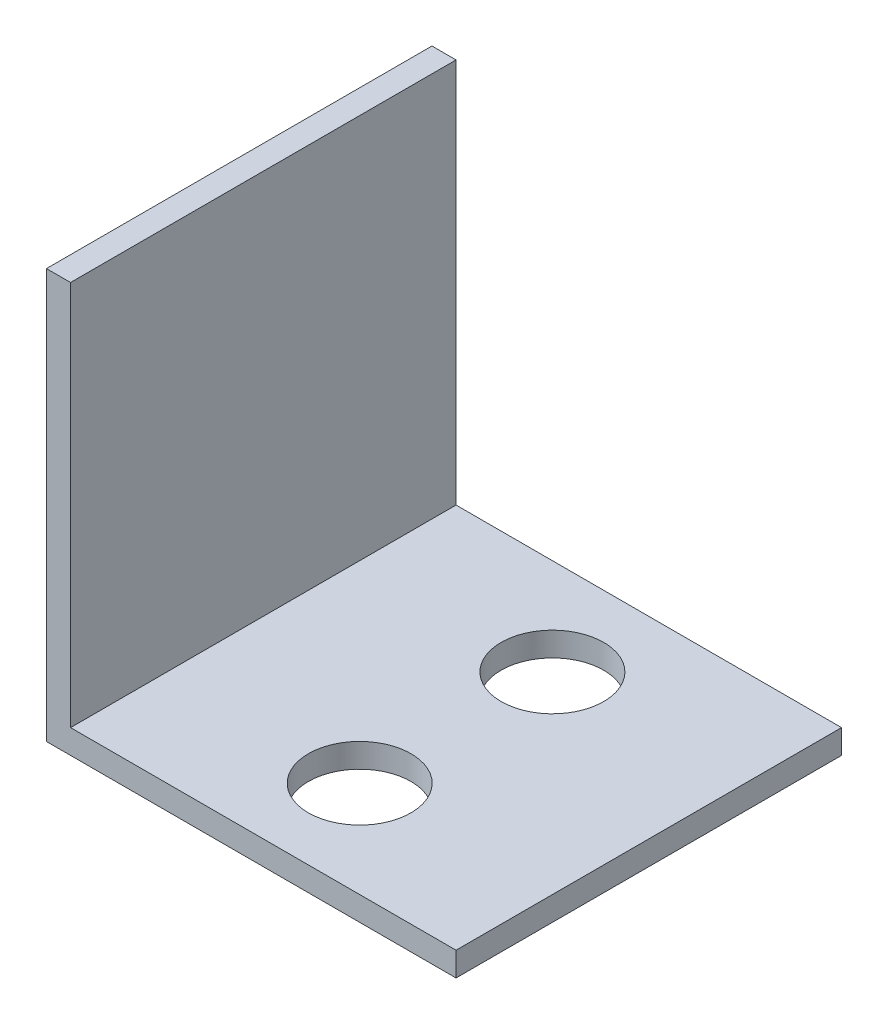
SolidWorks part; units mm, degrees
material "Alumina"
ref_plane "Front Plane" through (0, 0, 0) normal (0, 0, 1) x (1, 0, 0)
ref_plane "Top Plane" through (0, 0, 0) normal (0, 1, 0) x (1, 0, 0)
ref_plane "Right Plane" through (0, 0, 0) normal (1, 0, 0) x (0, 0, -1)
sketch "Sketch1" plane through (0, 0, 0) normal (0, 0, 1) x (1, 0, 0)
  line L0 (0, 0) -> (0, 25.4)
  line L1 (0, 25.4) -> (-1.5875, 25.4)
  line L2 (-1.5875, 25.4) -> (-1.5875, -1.5875)
  line L3 (-1.5875, -1.5875) -> (25.4, -1.5875)
  line L4 (25.4, -1.5875) -> (25.4, 0)
  line L5 (25.4, 0) -> (0, 0)
  dimension "D1" = 25.4
  dimension "D2" = 25.4
  dimension "D3" = 1.5875
  dimension "D4" = 1.5875
extrude "Boss-Extrude1" add sketch "Sketch1" along normal blind 25.4
sketch "Sketch2" plane through (0, 0, 0) normal (0, 1, 0) x (1, 0, 0)
  line L0 (0, -25.4) -> (0, 0) construction
  line L1 (25.4, 0) -> (0, 0) construction
  point P0 (12.7, -19.05)
  point P1 (12.7, -6.35)
  dimension "D1" = 12.7
  dimension "D2" = 12.7
  dimension "D3" = 6.35
hole_wizard "1/4 Clearance Hole1" positions "3DSketch1" profile "Sketch3" hole size "1/4" standard "ANSI Inch" end condition up to next
sketch3d "3DSketch1"
  point P0 (12.7, 0, 19.05)
  point P3 (12.7, 0, 6.35)
sketch "Sketch3" plane through (12.7, 0, 19.05) normal (1, 0, 0) x (0, 0, 1)
  line L0 (0, 0) -> (0, 1.5875)
  line L1 (0, 1.5875) -> (3.3782, 1.5875)
  line L2 (3.3782, 1.5875) -> (3.3782, 0)
  line L5 (3.3782, 0) -> (0, 0)
  line L11 (0, -6.35) -> (0, 107.95) construction
  dimension "Thru Hole Dia." = 6.7564
  dimension "Thru Hole Depth" = 1.5875
